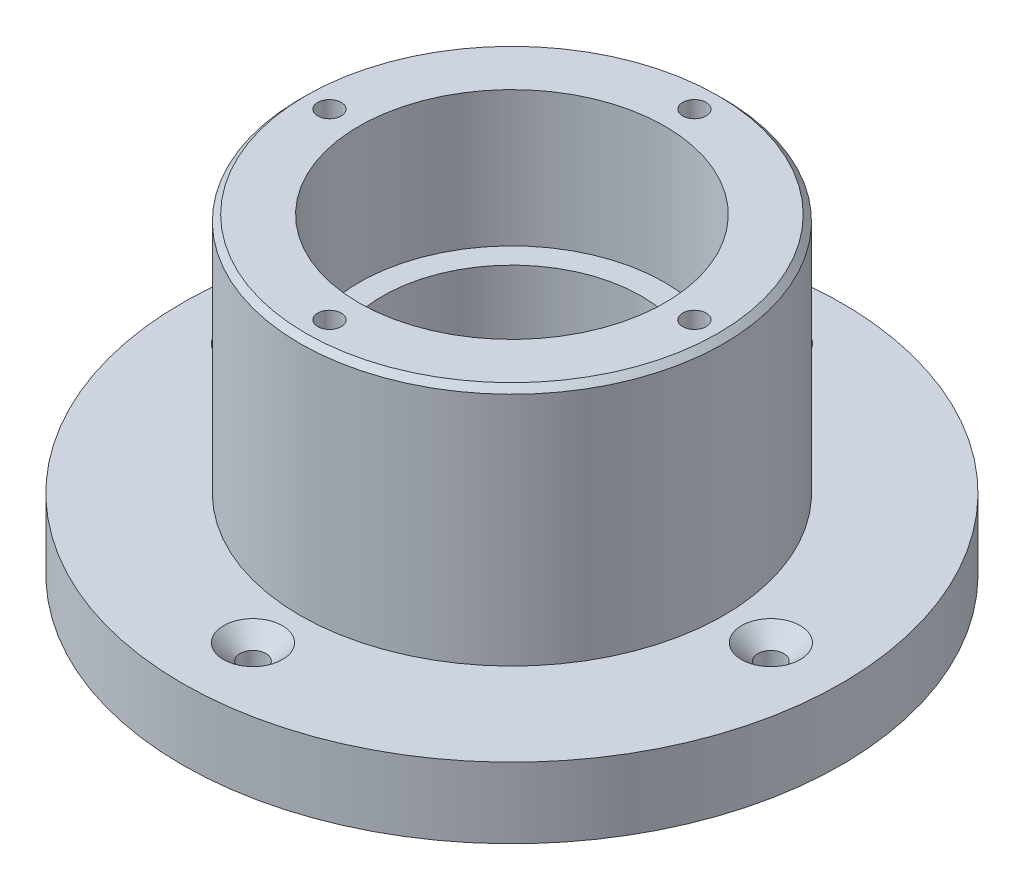
SolidWorks part; units mm, degrees
material "ABS"
ref_plane "Спереди" through (0, 0, 0) normal (0, 0, 1) x (1, 0, 0)
ref_plane "Сверху" through (0, 0, 0) normal (0, 1, 0) x (1, 0, 0)
ref_plane "Справа" through (0, 0, 0) normal (1, 0, 0) x (0, 0, -1)
sketch "Эскиз1" plane through (0, 0, 0) normal (0, 1, 0) x (1, 0, 0)
  circle A0 centre (0, 0) radius 26
  dimension "D1" = 52
extrude "Бобышка-Вытянуть1" add sketch "Эскиз1" along normal blind 4
sketch "Эскиз2" plane through (0, 4, 0) normal (0, 1, 0) x (1, 0, 0)
  circle A0 centre (0, 0) radius 18
  dimension "D1" = 36
extrude "Бобышка-Вытянуть2" add sketch "Эскиз2" along normal blind 20.5
sketch "Эскиз3" plane through (0, 24.5, 0) normal (0, 1, 0) x (1, 0, 0)
  circle A0 centre (0, 0) radius 13
  dimension "D1" = 26
extrude "Вырез-Вытянуть1" cut sketch "Эскиз3" along direction (0, 1, 0) on the side against the normal offset from surface (11.5 mm away) 13 up to face at (0, 0, 26)
sketch "Эскиз4" plane through (0, 4, 0) normal (0, 1, 0) x (1, 0, 0)
  circle A0 centre (0, 0) radius 22 construction
  circle A1 centre (-22, 0) radius 2.2
  circle A2 centre (0, 22) radius 2.2
  circle A3 centre (22, 0) radius 2.2
  circle A4 centre (0, -22) radius 2.2
  point P14 (0, 0)
  dimension "D1" = 44
  dimension "D2" = 4.4
  dimension "D3" = 4
sketch "Эскиз6" plane through (0, 13, 0) normal (0, 1, 0) x (1, 0, 0)
  circle A0 centre (0, 0) radius 11
  dimension "D1" = 22
extrude "Вырез-Вытянуть4" cut sketch "Эскиз6" against normal through all
sketch "Эскиз7" plane through (0, 24.5, 0) normal (0, 1, 0) x (1, 0, 0)
  circle A0 centre (0, 0) radius 15.5 construction
  circle A1 centre (-15.5, 0) radius 1
  circle A2 centre (0, 15.5) radius 1
  circle A3 centre (15.5, 0) radius 1
  circle A4 centre (0, -15.5) radius 1
  point P14 (0, 0)
  dimension "D1" = 31
  dimension "D2" = 2
extrude "Вырез-Вытянуть5" cut sketch "Эскиз7" against normal blind 5
sketch "Эскиз8" plane through (0, 4, 0) normal (0, 1, 0) x (1, 0, 0)
  circle A0 centre (0, 0) radius 26
  circle A1 centre (0, 0) radius 28
  dimension "D1" = 56
  dimension "D2" = 52
extrude "Бобышка-Вытянуть3" add sketch "Эскиз8" against normal blind 6
chamfer "Фаска1" distance 0.5 angle 45 1 edges at (0, -2, 26)
chamfer "Фаска2" distance 0.5 angle 45 1 edges at (0, 24.5, 18)
ref_axis "Ось1" through (0, -20.7688, 22) along (0, 1, 0)
sketch "Эскиз9" plane through (0, 0, 0) normal (1, 0, 0) x (0, 0, -1)
  line L1 (-22, -20.7688) -> (-22, 30.1347) construction
  line L2 (-20.9, 2.648) -> (-19.5, 4)
  line L3 (22, 4) -> (-22, 4) construction
  line L4 (-19.5, 4) -> (-22, 4)
  line L5 (-19.8, 4) -> (-24.2, 4) construction
  line L6 (-22, 2.648) -> (-22, 4)
  line L7 (-20.9, 2.648) -> (-20.9, -2)
  line L8 (-28, -2) -> (28, -2) construction
  line L9 (-20.9, -2) -> (-22, -2)
  line L10 (-22, -2) -> (-22, 2.648)
  point P4 (0, 0)
  dimension "D1" = 1.1
  dimension "D2" = 2.5
  dimension "D3" = 46
revolve "Вырез-Повернуть2" cut sketch "Эскиз9" angle 360 about axis through (0, -20.7688, 22) along (0, 1, 0)
pattern_circular "Круговой массив1" count 4 over 360 about axis through (0, 24.5, 0) along (0, -1, 0) of "Вырез-Повернуть2"
